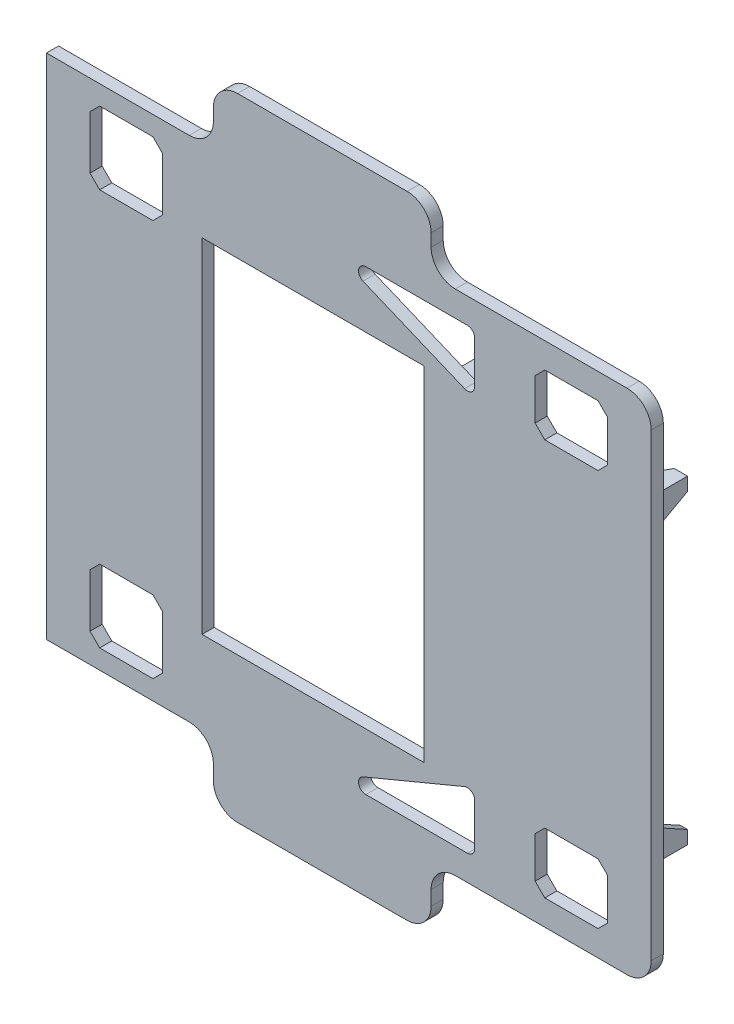
SolidWorks part; units mm, degrees
ref_plane "前视基准面" through (0, 0, 0) normal (0, 0, 1) x (1, 0, 0)
ref_plane "上视基准面" through (0, 0, 0) normal (0, 1, 0) x (1, 0, 0)
ref_plane "右视基准面" through (0, 0, 0) normal (1, 0, 0) x (0, 0, -1)
sketch "草图1" plane through (0, 0, 0) normal (0, 0, 1) x (1, 0, 0)
  line L0 (-45, 115) -> (-45, 120)
  line L1 (-114, 105) -> (-55, 105)
  line L2 (-114, 95) -> (-114, -95)
  line L3 (-114, -105) -> (-55, -105)
  line L4 (136, 95) -> (136, -95)
  line L5 (-114, 95) -> (-114, 105)
  line L7 (-35, 130) -> (35.1247, 130)
  line L8 (45, 120.1247) -> (45, 115)
  line L9 (-45, -115) -> (-45, -121.0101)
  line L10 (-35, -131.0101) -> (35, -131.0101)
  line L11 (45, -121.0101) -> (45, -115)
  line L12 (55, 105) -> (126, 105)
  line L13 (55, -105) -> (115, -105)
  line L15 (132.8114, 102.3216) -> (136, 105) construction
  line L16 (-159.0816, 0) -> (162.8742, 0) construction
  line L17 (0, -160.1649) -> (0, 164.862) construction
  line L18 (-114, -95) -> (-114, -105)
  line L22 (126, -105) -> (115, -105)
  arc A2 (136, 95) -> (126, 105) centre (126, 95) ccw
  arc A4 (-55, 105) -> (-45, 115) centre (-55, 115) ccw
  arc A5 (55, 105) -> (45, 115) centre (55, 115) cw
  arc A6 (-35, 130) -> (-45, 120) centre (-35, 120) ccw
  arc A7 (45, 120.1247) -> (35.1247, 130) centre (35.1247, 120.1247) ccw
  arc A8 (-45, -115) -> (-55, -105) centre (-55, -115) ccw
  arc A9 (45, -115) -> (55, -105) centre (55, -115) cw
  arc A10 (-35, -131.0101) -> (-45, -121.0101) centre (-35, -121.0101) cw
  arc A11 (35, -131.0101) -> (45, -121.0101) centre (35, -121.0101) ccw
  arc A13 (126, -105) -> (136, -95) centre (126, -95) ccw
  point P0 (0, 0)
  point P28 (-45.35, 105)
  point P32 (45, 105)
  point P40 (45, -105)
  dimension "D2" = 45
  dimension "D3" = 10
  dimension "D4" = 45
  dimension "D5" = 10
  dimension "D6" = 10
  dimension "D9" = 10
  dimension "D11" = 9.8753
  dimension "D7" = 10
  dimension "D8" = 10
  dimension "D10" = 10
  dimension "D12" = 10
  dimension "D13" = 210
  dimension "D14" = 59
  dimension "D15" = 59
extrude "凸台-拉伸1" add sketch "草图1" along normal blind 5
sketch "草图2" plane through (0, 0, 5) normal (0, 0, 1) x (1, 0, 0)
  line L0 (136, -95) -> (136, 95) construction
  line L1 (-96, 97) -> (-66, 97)
  line L2 (-96, 97) -> (-96, 67)
  line L3 (-96, 67) -> (-66, 67)
  line L4 (-66, 97) -> (-66, 67)
  line L5 (-96, 97) -> (-66, 67) construction
  line L6 (-96, 67) -> (-66, 97) construction
  line L7 (-96, -67) -> (-66, -67)
  line L8 (-96, -67) -> (-96, -97)
  line L9 (-96, -97) -> (-66, -97)
  line L10 (-66, -67) -> (-66, -97)
  line L11 (-96, -67) -> (-66, -97) construction
  line L12 (-96, -97) -> (-66, -67) construction
  line L13 (88, 94.5) -> (118, 94.5)
  line L14 (88, 94.5) -> (88, 69.5)
  line L15 (88, 69.5) -> (118, 69.5)
  line L16 (118, 94.5) -> (118, 69.5)
  line L17 (88, 94.5) -> (118, 69.5) construction
  line L18 (88, 69.5) -> (118, 94.5) construction
  line L19 (88, -69.5) -> (118, -69.5)
  line L20 (88, -69.5) -> (88, -94.5)
  line L21 (88, -94.5) -> (118, -94.5)
  line L22 (118, -69.5) -> (118, -94.5)
  line L23 (88, -69.5) -> (118, -94.5) construction
  line L24 (88, -94.5) -> (118, -69.5) construction
  line L25 (3, 94.5) -> (63, 94.5)
  line L28 (63, 94.5) -> (63, 69.5)
  line L29 (3, 94.5) -> (63, 69.5) construction
  line L30 (33, 82) -> (63, 94.5) construction
  line L33 (3, -94.5) -> (63, -94.5)
  line L34 (63, -69.5) -> (63, -94.5)
  line L35 (33, -82) -> (63, -94.5) construction
  line L36 (3, -94.5) -> (63, -69.5) construction
  line L37 (-55, 105) -> (-114, 105) construction
  line L38 (-114, -105) -> (-55, -105) construction
  line L39 (-114, 105) -> (-114, -105) construction
  line L40 (3, 94.5) -> (63, 69.5)
  line L41 (3, -94.5) -> (63, -69.5)
  point P0 (-81, 82)
  point P5 (-81, -82)
  point P10 (103, 82)
  point P15 (103, -82)
  point P20 (33, 82)
  point P25 (33, -82)
  dimension "D1" = 8
  dimension "D2" = 8
  dimension "D3" = 18
  dimension "D4" = 18
  dimension "D5" = 30
  dimension "D6" = 30
  dimension "D7" = 18
  dimension "D8" = 18
  dimension "D9" = 25
  dimension "D10" = 30
  dimension "D12" = 60
  dimension "D13" = 25
  dimension "D14" = 30
  dimension "D15" = 30
  dimension "D16" = 25
  dimension "D17" = 25
  dimension "D18" = 25
  dimension "D19" = 25
extrude "切除-拉伸1" cut sketch "草图2" against normal through all
chamfer "倒角1" distance 4 angle 45 16 edges at (-96, 67, 2.5) (-96, -97, 2.5) (88, -94.5, 2.5) (-96, 97, 2.5) (-96, -67, 2.5) (88, -69.5, 2.5) (-66, -97, 2.5) (-66, 67, 2.5) (118, -94.5, 2.5) (-66, -67, 2.5) (118, -69.5, 2.5) (-66, 97, 2.5) (88, 69.5, 2.5) (88, 94.5, 2.5) (118, 69.5, 2.5) (118, 94.5, 2.5)
sketch "草图3" plane through (0, 0, 0) normal (0, 0, -1) x (-1, 0, 0)
  line L0 (-166.2651, 0) -> (135.0615, 0) construction
  line L1 (-131, 66) -> (-131, 55)
  line L2 (-131, 55) -> (-128, 55)
  line L3 (-128, 55) -> (-128, 63)
  line L4 (-128, 63) -> (-120, 63)
  line L5 (-120, 63) -> (-120, 66)
  line L6 (-120, 66) -> (-131, 66)
  line L7 (-56, 63) -> (-56, 66)
  line L8 (-56, 66) -> (-45, 66)
  line L9 (-45, 66) -> (-45, 55)
  line L10 (-45, 55) -> (-48, 55)
  line L11 (-48, 55) -> (-48, 63)
  line L12 (-48, 63) -> (-56, 63)
  line L13 (-136, -95) -> (-136, 95) construction
  line L14 (-48, -63) -> (-56, -63)
  line L15 (-48, -55) -> (-48, -63)
  line L16 (-45, -55) -> (-48, -55)
  line L17 (-45, -66) -> (-45, -55)
  line L18 (-56, -63) -> (-56, -66)
  line L19 (-120, -63) -> (-120, -66)
  line L20 (-128, -63) -> (-120, -63)
  line L21 (-128, -55) -> (-128, -63)
  line L22 (-131, -55) -> (-128, -55)
  line L23 (-131, -66) -> (-131, -55)
  line L24 (-120, -66) -> (-131, -66)
  line L25 (-56, -66) -> (-45, -66)
  dimension "D1" = 3
  dimension "D2" = 3
  dimension "D3" = 3
  dimension "D4" = 3
  dimension "D5" = 80
  dimension "D6" = 63
  dimension "D7" = 8
  dimension "D8" = 5
extrude "凸台-拉伸2" add sketch "草图3" along normal blind 15
sketch "草图4" plane through (131, 0, 0) normal (1, 0, 0) x (0, 0, -1)
  line L0 (15, 60.5) -> (5, 55)
  line L1 (15, 66) -> (15, 55) construction
  line L2 (15, 55) -> (0, 55) construction
  line L3 (5, 55) -> (15, 55)
  line L4 (15, 55) -> (15, 60.5)
  line L5 (15, -60.5) -> (15, -55)
  line L6 (15, -55) -> (15, -66) construction
  line L7 (15, -55) -> (5, -55)
  line L8 (15, -55) -> (0, -55) construction
  line L9 (5, -55) -> (15, -60.5)
  dimension "D1" = 10
  dimension "D2" = 10
extrude "切除-拉伸2" cut sketch "草图4" against normal blind 3
sketch "草图5" plane through (0, 66, 0) normal (0, 1, 0) x (1, 0, 0)
  line L0 (50.5, 15) -> (56, 15)
  line L1 (45, 15) -> (56, 15) construction
  line L2 (56, 15) -> (56, 5)
  line L3 (56, 15) -> (56, 0) construction
  line L4 (56, 5) -> (50.5, 15)
  line L5 (120, 15) -> (125.5, 15)
  line L6 (120, 15) -> (131, 15) construction
  line L7 (125.5, 15) -> (120, 5)
  line L8 (120, 15) -> (120, 0) construction
  line L9 (120, 5) -> (120, 15)
  dimension "D1" = 10
  dimension "D2" = 10
extrude "切除-拉伸3" cut sketch "草图5" against normal blind 3
sketch "草图6" plane through (45, 0, 0) normal (-1, 0, 0) x (0, 0, 1)
  line L0 (-15, 60.5) -> (-5, 55)
  line L1 (-15, 55) -> (-15, 66) construction
  line L2 (-5, 55) -> (-15, 55)
  line L3 (-15, 55) -> (-15, 60.5)
  line L4 (-15, -60.5) -> (-15, -55)
  line L5 (-15, -55) -> (-5, -55)
  line L6 (-15, -55) -> (0, -55) construction
  line L7 (-5, -55) -> (-15, -60.5)
  dimension "D1" = 10
extrude "切除-拉伸4" cut sketch "草图6" against normal blind 3
sketch "草图7" plane through (0, -66, 0) normal (0, -1, 0) x (1, 0, 0)
  line L0 (50.5, -15) -> (56, -15)
  line L1 (56, -15) -> (45, -15) construction
  line L2 (56, -15) -> (56, -5)
  line L3 (56, -5) -> (50.5, -15)
  line L4 (120, -15) -> (125.5, -15)
  line L5 (131, -15) -> (120, -15) construction
  line L6 (125.5, -15) -> (120, -5)
  line L7 (120, -5) -> (120, -15)
extrude "切除-拉伸5" cut sketch "草图7" against normal blind 3
fillet "圆角1" radius 3 6 edges at (63, 69.5, 2.5) (3, -94.5, 2.5) (3, 94.5, 2.5) (63, -94.5, 2.5) (63, -69.5, 2.5) (63, 94.5, 2.5)
sketch "草图8" plane through (0, 0, 0) normal (0, 0, -1) x (-1, 0, 0)
  line L0 (-42, 71) -> (-42, -71)
  line L1 (-42, -71) -> (49.7, -71)
  line L2 (49.7, -71) -> (49.7, 71)
  line L3 (49.7, 71) -> (-42, 71)
  line L4 (-136, -95) -> (-136, 95) construction
  line L5 (-187.6753, 0) -> (145.1783, 0) construction
  point P9 (49.7, 0)
  dimension "D1" = 94
  dimension "D2" = 142
  dimension "D3" = 91.7
extrude "切除-拉伸6" cut sketch "草图8" against normal blind 5
equation "\"45、\"=43.7672"
